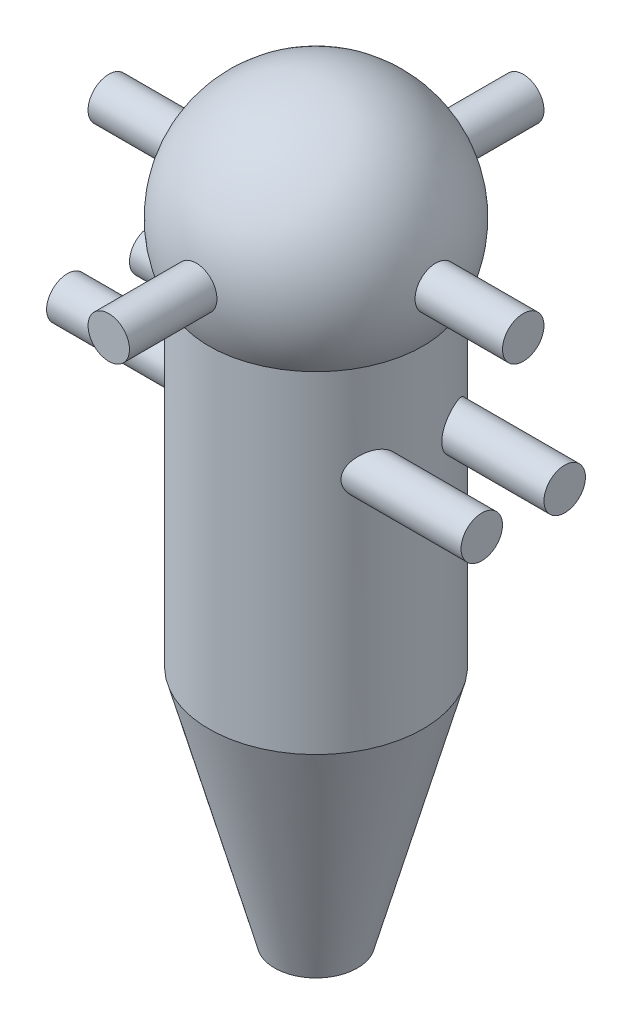
SolidWorks part; units mm, degrees
ref_plane "Front Plane" through (0, 0, 0) normal (0, 0, 1) x (1, 0, 0)
ref_plane "Top Plane" through (0, 0, 0) normal (0, 1, 0) x (1, 0, 0)
ref_plane "Right Plane" through (0, 0, 0) normal (1, 0, 0) x (0, 0, -1)
sketch "Sketch1" plane through (0, 0, 0) normal (0, 0, 1) x (1, 0, 0)
  line L0 (0, 0) -> (0, 72.4784) construction
  line L1 (-7.75, 54.2126) -> (-7.75, 30.2126)
  line L2 (-7.75, 30.2126) -> (-3, 12.8507)
  line L3 (0, 67.1813) -> (0, 12.8507)
  line L4 (-3, 12.8507) -> (0, 12.8507)
  arc A0 (-7.75, 54.2126) -> (0, 67.1813) centre (0, 58.3813) cw
  dimension "D2" = 8.8
  dimension "D1" = 7.75
  dimension "D3" = 24
  dimension "D4" = 3
  dimension "D5" = 18
revolve "Revolve1" add sketch "Sketch1" angle 360 about L0
sketch "Sketch2" plane through (0, 0, 0) normal (0, 0, 1) x (1, 0, 0)
  spline S0 degree 3 poles (0, 16.2683) (-0.1464, 11.5568) (-1.6086, -4.8726) (12.4029, -17.475) (3.1453, -27.7902) knots 0 0 0 0 0.30084 1 1 1 1
sketch "Sketch3" plane through (0, 0, 0) normal (1, 0, 0) x (0, 0, -1)
  spline S0 degree 3 poles (0, 16.2683) (0.3589, 2.2168) (-3.8384, -13.5019) (6.0872, -25.7366) knots 0 0 0 0 1 1 1 1
curve "Curve1"
sweep "Sweep1" [suppressed] add path "Curve1" circular profile diameter 6 parameters "D3"=6
sketch "Sketch4" plane through (0, 0, 0) normal (0, 0, 1) x (1, 0, 0)
  line L0 (0, 75.4963) -> (0, -9.8478) construction
  line L1 (0, 0) -> (0, 72.4784) construction
  circle A0 centre (0, 58.3813) radius 1.5
extrude "Boss-Extrude1" add sketch "Sketch4" along normal blind 15 and the other way blind 15
sketch "Sketch6" plane through (0, 0, 0) normal (1, 0, 0) x (0, 0, -1)
  line L1 (4.7922, 47.3813) -> (-3.3955, 47.3813) construction
  line L2 (0, 67.1813) -> (0, 12.8507) construction
  line L3 (0, 50.0767) -> (0, 43.1261) construction
  line L4 (0, 0) -> (0, 72.4784) construction
  circle A0 centre (0, 58.3813) radius 1.5
  circle A1 centre (0, 58.3813) radius 6 construction
  circle A2 centre (3, 47.3813) radius 1.5
  circle A3 centre (-3, 47.3813) radius 1.5
  dimension "D1" = 11
  dimension "D2" = 3
extrude "Boss-Extrude2" add sketch "Sketch6" along normal blind 15 and the other way blind 15
